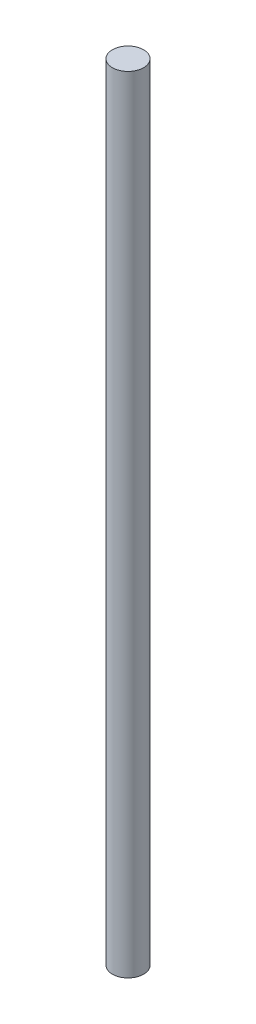
SolidWorks part; units mm, degrees
material "6061-T6 (SS)"
ref_plane "Front Plane" through (0, 0, 0) normal (0, 0, 1) x (1, 0, 0)
ref_plane "Top Plane" through (0, 0, 0) normal (0, 1, 0) x (1, 0, 0)
ref_plane "Right Plane" through (0, 0, 0) normal (1, 0, 0) x (0, 0, -1)
sketch "Sketch1" plane through (0, 0, 0) normal (0, 1, 0) x (1, 0, 0)
  circle A0 centre (0, 0) radius 4
  dimension "D1" = 8
extrude "Boss-Extrude1" add sketch "Sketch1" along normal mid plane 201.425
